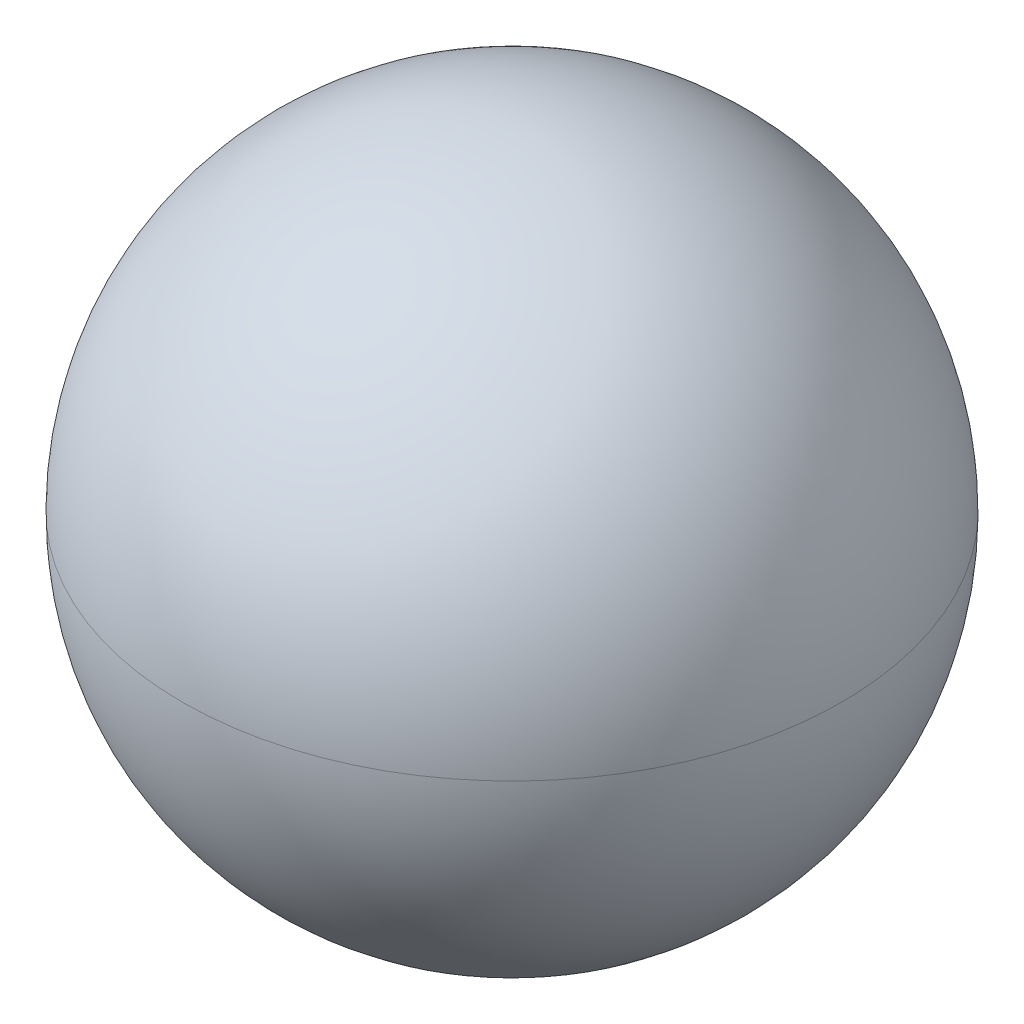
SolidWorks part; units mm, degrees
ref_plane "Front Plane" through (0, 0, 0) normal (0, 0, 1) x (1, 0, 0)
ref_plane "Top Plane" through (0, 0, 0) normal (0, 1, 0) x (1, 0, 0)
ref_plane "Right Plane" through (0, 0, 0) normal (1, 0, 0) x (0, 0, -1)
sketch "Sketch1" plane through (0, 0, 0) normal (0, 1, 0) x (1, 0, 0)
  circle A0 centre (0, 0) radius 274.32
  dimension "D1" = 548.64
extrude "Boss-Extrude1" add sketch "Sketch1" along normal blind 548.64
fillet "Fillet1" radius 274.32 2 edges at (0, 0, 274.32) (0, 548.64, 274.32)
shell "Shell2" thickness 3.175
